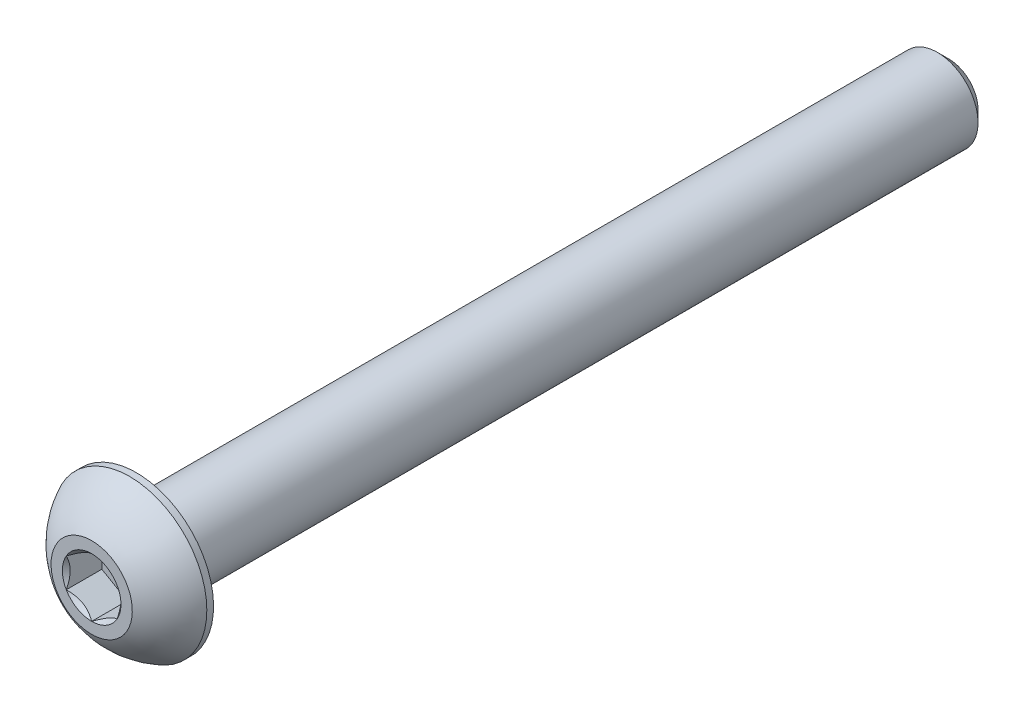
SolidWorks part; units mm, degrees
material "Alloy Steel"
ref_plane "Front Plane" through (0, 0, 0) normal (0, 0, 1) x (1, 0, 0)
ref_plane "Top Plane" through (0, 0, 0) normal (0, 1, 0) x (1, 0, 0)
ref_plane "Right Plane" through (0, 0, 0) normal (1, 0, 0) x (0, 0, -1)
sketch "Sketch1" plane through (0, 0, 0) normal (1, 0, 0) x (0, 0, -1)
  line L0 (-21.1, 0) -> (21.1, 0) construction
  line L1 (-18.9, 3.8) -> (-18.9, -3.8) construction
  line L2 (21.1, 2) -> (21.1, -2) construction
  line L3 (21.0563, 2.0758) -> (21.4063, 1.4696) construction
  line L4 (21.4063, 1.4696) -> (21.7563, 2.0758) construction
  line L5 (21.7563, 2.0758) -> (21.0563, 2.0758) construction
  line L6 (21.1, 2) -> (21.7125, 2) construction
  line L7 (21.4062, 2.0758) -> (21.4062, 2) construction
  line L8 (21.4062, 2) -> (21.4062, 1.5453) construction
  line L9 (21.4062, 1.5453) -> (21.4063, 1.4696) construction
  line L10 (21.3625, 1.5453) -> (21.45, 1.5453)
  line L11 (21.0781, 2.0379) -> (21.7344, 2.0379)
  line L12 (21.45, 1.5453) -> (21.7344, 2.0379)
  line L13 (21.3625, 1.5453) -> (21.0781, 2.0379)
  line L14 (-21.1, 1.25) -> (-21.1, -1.25) construction
  line L15 (21.1, 2) -> (-18.9, 2) construction
  point P3 (-18.9, 0)
  point P6 (-19.35, 0)
  point P21 (21.4062, 2.0379)
  point P24 (-19.23, 3.8)
  point P25 (19.35, -2)
  point P26 (-21.1, 2)
  dimension "Head Height" = 2.2
  dimension "Length" = 40
  dimension "Head Dia" = 7.6
  dimension "Thread Dia" = 4
  dimension "Pitch" = 0.7
  dimension "D2" = 0.0875
  dimension "Drive Size" = 2.5
  dimension "D1" = 1.75
  dimension "D3" = 0.33
  dimension "D4" = 1.75
sketch "Sketch2" plane through (0, 0, 0) normal (1, 0, 0) x (0, 0, -1)
  line L0 (-21.1, 0) -> (21.1, 0)
  line L1 (21.1, 0) -> (21.1, 1.44)
  line L2 (21.1, 2) -> (21.1, -2) construction
  line L3 (21.1, 1.44) -> (20.54, 2)
  line L4 (20.54, 2) -> (-18.9, 2)
  line L5 (-18.9, 3.8) -> (-18.9, -3.8) construction
  line L6 (-18.9, 2) -> (-18.9, 3.8)
  line L7 (-18.9, 3.8) -> (-19.23, 3.8)
  line L8 (21.1, 2) -> (21.7125, 2) construction
  line L9 (-21.1, 0) -> (-21.1, 2)
  arc A0 (-21.1, 2) -> (-19.23, 3.8) centre (-17.3736, 0) cw
  dimension "D1" = 0.56
  dimension "D2" = 45
revolve "Revolve1" add sketch "Sketch2" angle 360 about L0
sketch "Sketch3" plane through (0, 0, 21.1) normal (0, 0, 1) x (1, 0, 0)
  line L1 (0, 1.4434) -> (-1.25, 0.7217)
  line L2 (-1.25, 0.7217) -> (-1.25, -0.7217)
  line L3 (-1.25, -0.7217) -> (0, -1.4434)
  line L4 (0, -1.4434) -> (1.25, -0.7217)
  line L5 (1.25, -0.7217) -> (1.25, 0.7217)
  line L6 (1.25, 0.7217) -> (0, 1.4434)
  circle A0 centre (0, 0) radius 1.25 construction
  dimension "D1" = 2.5
extrude "Cut-Extrude1" cut sketch "Sketch3" against normal up to vertex (1.75 mm away) up to point (0, 0, 19.35)
sketch "Sketch4" plane through (0, 0, 21.1) normal (0, 0, 1) x (1, 0, 0)
  circle A0 centre (0, 0) radius 1.4434
extrude "Cut-Extrude2" cut sketch "Sketch4" against normal blind 10 draft 45
split "Split1" [suppressed] bodies to split 106
sketch "Sketch5" [suppressed] plane through (0, 0, -21.1) normal (0, 0, -1) x (-1, 0, 0)
  circle A0 centre (0, 0) radius 2 construction
  circle A1 centre (0, 0) radius 2
curve "Helix/Spiral1" [suppressed] pitch 0.7 height 40.7 turns 58.1429
sketch "Sketch6" [suppressed] plane through (0, 0, 0) normal (1, 0, 0) x (0, 0, -1)
  line L0 (21.3625, 1.5453) -> (21.45, 1.5453) construction
  line L1 (21.3625, 1.5453) -> (21.0781, 2.0379) construction
  line L2 (21.0781, 2.0379) -> (21.7344, 2.0379) construction
  line L3 (21.45, 1.5453) -> (21.7344, 2.0379) construction
  line L4 (21.3625, 1.5453) -> (21.45, 1.5453)
  line L5 (21.3625, 1.5453) -> (21.0781, 2.0379)
  line L6 (21.0781, 2.0379) -> (21.7344, 2.0379)
  line L7 (21.45, 1.5453) -> (21.7344, 2.0379)
sweep "Cut-Sweep1" [suppressed] cut profiles "Sketch6" path "Helix/Spiral1"
sketch "Sketch7" [suppressed] plane through (0, 0, 18.9) normal (0, 0, -1) x (-1, 0, 0)
  circle A1 centre (0, 0) radius 2
  circle A2 centre (0, 0) radius 2
  dimension "D1" = 0
extrude "Boss-Extrude1" [suppressed] add sketch "Sketch7" along normal blind 10 draft 30
equation "\"D2@Sketch1\" = \"Pitch@Sketch1\" / 8"
equation "\"D1@Sketch1\"=\"Drive Size@Sketch1\"*.7"
equation "\"D3@Sketch1\"=\"Head Height@Sketch1\"*.15"
equation "\"D1@Sketch2\"=\"Pitch@Sketch1\"*.8"
equation "\"D1@Sketch3\"=\"Drive Size@Sketch1\""
equation "\"D4@Helix/Spiral1\"=\"Pitch@Sketch1\""
equation "\"D3@Helix/Spiral1\"=\"Length@Sketch1\"+\"Pitch@Sketch1\""
equation "\"D4@Sketch1\"=\"Pitch@Sketch1\"*2.5"
